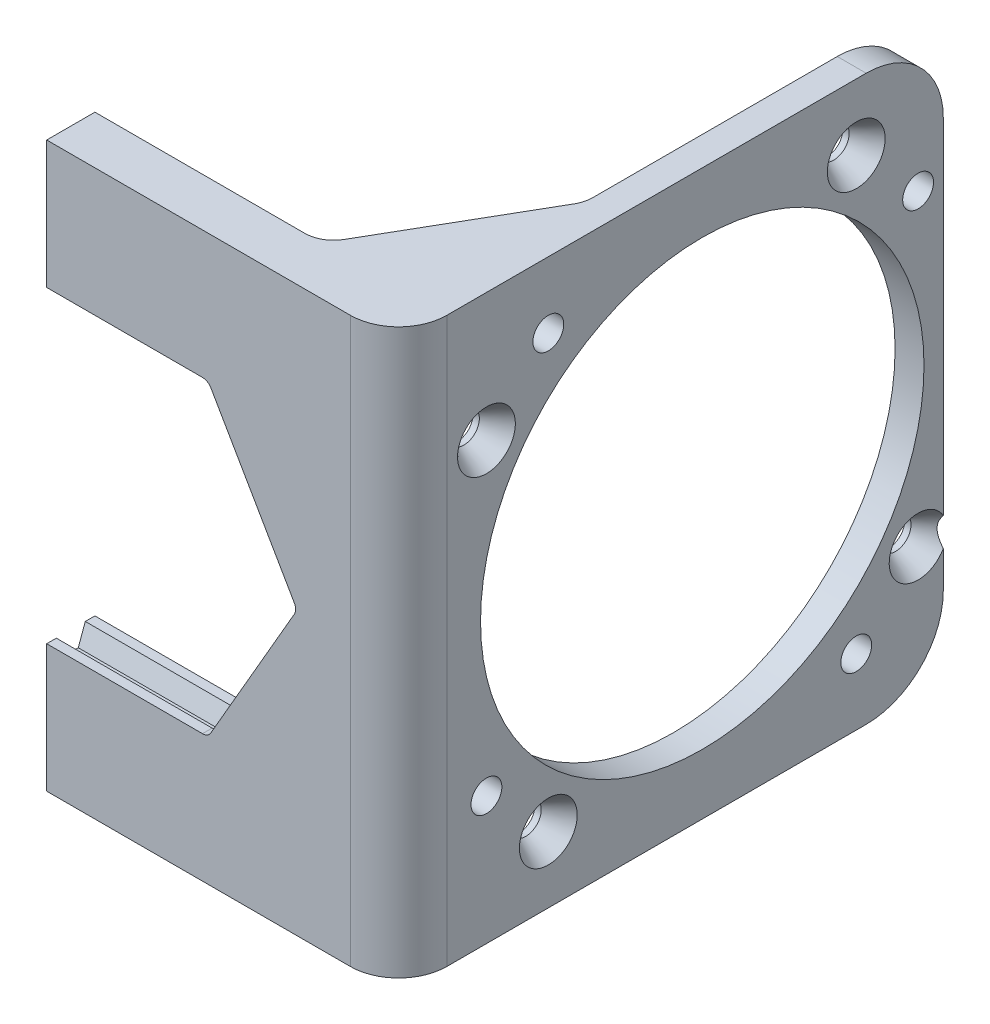
SolidWorks part; units mm, degrees
material "6061 合金"
ref_plane "前视基准面" through (0, 0, 0) normal (0, 0, 1) x (1, 0, 0)
ref_plane "上视基准面" through (0, 0, 0) normal (0, 1, 0) x (1, 0, 0)
ref_plane "右视基准面" through (0, 0, 0) normal (1, 0, 0) x (0, 0, -1)
other "Configuration Table"
sketch "草图1" plane through (0, 0, 0) normal (0, 0, 1) x (1, 0, 0)
  line L0 (-10.7623, 0) -> (8.7048, 0) construction
  line L1 (0, 6.2516) -> (0, -8.3883) construction
  circle A0 centre (0, 0) radius 18
  dimension "D1" = 36
extrude "凸台-拉伸1" add sketch "草图1" along normal blind 5
sketch "草图8" plane through (0, 0, 0) normal (0, 0, 1) x (1, 0, 0)
  line L0 (37.5243, 0) -> (-36.7763, 0) construction
  line L1 (0, 34.2207) -> (0, -32.974) construction
  line L2 (0, 26.25) -> (31, 26.25)
  line L3 (31, 26.25) -> (31, -26.25)
  line L4 (31, -26.25) -> (0, -26.25)
  line L5 (0, -26.25) -> (0, -18)
  line L6 (0, 26.25) -> (0, 18)
  circle A0 centre (0, 0) radius 18 construction
  arc A1 (0, -18) -> (0, 18) centre (0, 0) ccw
  dimension "D1" = 52.5
  dimension "D2" = 31
extrude "凸台-拉伸2" add sketch "草图8" along normal up to surface (5 mm away) up to face at (18, 0, 5)
sketch "草图9" plane through (0, 0, 0) normal (0, 0, -1) x (-1, 0, 0)
  line L0 (-31, 26.25) -> (0, 26.25) construction
  line L1 (-31, -26.25) -> (-26, -26.25)
  line L2 (-31, -26.25) -> (-31, 26.25)
  line L3 (-31, 26.25) -> (-26, 26.25)
  line L4 (-26, -26.25) -> (-26, 26.25)
  dimension "D1" = 5
extrude "凸台-拉伸3" add sketch "草图9" along normal blind 51.5
sketch "草图12" plane through (31, 0, 0) normal (1, 0, 0) x (0, 0, -1)
  line L1 (26.5, 0) -> (48.8882, 15.9693) construction
  line L2 (42.4693, 22.3882) -> (26.5, 0) construction
  line L3 (-6.3808, 0) -> (26.5, 0) construction
  line L4 (26.5, 0) -> (4.1118, 15.9693) construction
  line L5 (-5, -26.25) -> (-5, 26.25) construction
  circle A0 centre (26.5, 0) radius 27.5 construction
  circle A1 centre (4.1118, 15.9693) radius 1.6
  circle A2 centre (42.4693, 22.3882) radius 1.6
  circle A3 centre (48.8882, -15.9693) radius 1.6
  circle A4 centre (10.5307, -22.3882) radius 1.6
  circle A5 centre (48.8882, 15.9693) radius 1.6
  circle A6 centre (42.4693, -22.3882) radius 1.6
  circle A7 centre (4.1118, -15.9693) radius 1.6
  circle A8 centre (10.5307, 22.3882) radius 1.6
  point P22 (26.5, 0)
  point P27 (26.5, 0)
  dimension "D2" = 55
  dimension "D4" = 3.2
  dimension "D1" = 31.5
  dimension "D3" = 35.5
  dimension "D6" = 19
  dimension "D5" = 4
  dimension "D7" = 4
extrude "切除-拉伸1" cut sketch "草图12" against normal blind 45
sketch "草图25" plane through (0, 0, 0) normal (0, 0, -1) x (-1, 0, 0)
  line L0 (0, 16) -> (0, 26.25)
  line L1 (18.4752, 0) -> (9.2376, 16)
  line L2 (9.2376, 16) -> (-9.2376, 16)
  line L3 (-9.2376, 16) -> (-18.4752, 0)
  line L4 (-18.4752, 0) -> (-9.2376, -16)
  line L5 (-9.2376, -16) -> (9.2376, -16)
  line L6 (9.2376, -16) -> (18.4752, 0)
  line L7 (0, 26.25) -> (23.9717, 26.25)
  line L8 (23.9717, 26.25) -> (23.9717, -26.25)
  line L9 (23.9717, -26.25) -> (0, -26.25)
  line L10 (0, -26.25) -> (0, -16)
  circle A0 centre (0, 0) radius 16 construction
  line M6 (0, -26.25) -> (0, -18)
  arc M7 (0, -18) -> (0, 18) centre (0, 0) ccw
  line M8 (0, 18) -> (0, 26.25)
  dimension "D1" = 32
extrude "切除-拉伸7" cut sketch "草图25" against normal blind 10 contours L9 L8 L7 L2 L1 L6 L5 M8 M7 M6 | L1 M7 | L2 L0 M7 | L6 M7 | L10 L5 M7 region at (-3.1166, 16.8039, 0) region at (-0.5771, 22.125, 0) region at (-14.5526, 8.402, 0) region at (-3.1166, -16.8039, 0) region at (-14.5526, -8.402, 0)
extrude "切除-拉伸8" cut sketch "草图25<3>" against normal blind 10 contours L6 L1 L2 L3 L4 L5 M7 | L1 | L5 | L3 region at (0.0165, 0, 0) region at (-9.077, 15.7217, 0) region at (-9.077, -15.7217, 0)
sketch "草图25<3>" plane through (0, 0, 0) normal (0, 0, -1) x (-1, 0, 0) same geometry as "草图25"
sketch "草图26" plane through (0, 0, 0) normal (0, 0, -1) x (-1, 0, 0)
  line L0 (0, 26.25) -> (7.5, 26.25)
  line L1 (7.5, 26.25) -> (7.5, 16)
  line L2 (7.5, 16) -> (0, 16)
  line L3 (0, 16) -> (0, 26.25)
  line L4 (0, -16) -> (7.5, -16)
  line L5 (0, -16) -> (0, -26.25) construction
  line L6 (0, -16) -> (0, -26.25)
  line L7 (0, -26.25) -> (7.5, -26.25)
  line L8 (7.5, -26.25) -> (7.5, -16)
  dimension "D1" = 7.5
extrude "凸台-拉伸5" add sketch "草图26" against normal up to surface (5 mm away) up to face at (10.9945, 0, 5)
sketch "草图27" plane through (-7.5, 0, 0) normal (-1, 0, 0) x (0, 0, 1)
  line L0 (2.5, 16) -> (2.5, 50016) construction
  line L1 (5, 16) -> (0, 16) construction
  line L2 (1, 16) -> (1.7279, 18)
  line L3 (5, 16) -> (0, 16) construction
  line L4 (1.7279, 18) -> (2.5, 18)
  line L5 (3.2721, 18) -> (2.5, 18)
  line L6 (4, 16) -> (3.2721, 18)
  line L7 (1, 16) -> (4, 16)
  point P4 (2.5, 16)
  dimension "D1" = 3
  dimension "D2" = 40
  dimension "D3" = 2
ref_plane "基准面1" through (0, 0, 2.5) normal (0, 0, 1) x (1, 0, 0)
sketch "草图28" plane through (0, 0, 2.5) normal (0, 0, 1) x (1, 0, 0)
  line L0 (-7.5, -199984) -> (-7.5, 250016) construction
  line L1 (18.4752, 0) -> (9.2376, 16)
  line L2 (9.2376, 16) -> (-9.2376, 16)
  line L3 (-9.2376, 16) -> (-18.4752, 0)
  line L4 (-18.4752, 0) -> (-9.2376, -16)
  line L5 (-9.2376, -16) -> (9.2376, -16)
  line L6 (9.2376, -16) -> (18.4752, 0)
  circle A0 centre (0, 0) radius 16 construction
  dimension "D1" = 32
sweep "切除-扫描1" cut profiles "草图27" path "草图28"
fillet "圆角11" radius 1 12 edges at (10.3923, 18, 2.114) (10.3923, -18, 2.114) (20.7846, 0, 2.114) (9.2376, 16, 4.5) (10.3923, 18, 2.886) (9.2376, 16, 0.5) (9.2376, -16, 4.5) (10.3923, -18, 2.886) (9.2376, -16, 0.5) (18.4752, 0, 4.5) (20.7846, 0, 2.886) (18.4752, 0, 0.5)
sketch "草图14" plane through (31, 0, 0) normal (1, 0, 0) x (0, 0, -1)
  circle A0 centre (26.5, 0) radius 23
  dimension "D1" = 46
extrude "切除-拉伸2" cut sketch "草图14" against normal through all
sketch "草图21" plane through (0, 26.25, 0) normal (0, 1, 0) x (1, 0, 0)
  line L2 (26, 51.5) -> (26, 0) construction
  line L5 (-7.5, 0) -> (16, 0)
  line L6 (-7.5, -5) -> (31, -5)
  line L7 (31, -5) -> (31, 51.5)
  line L8 (31, 51.5) -> (26, 51.5)
  line L9 (26, 51.5) -> (26, 0)
  line L10 (26, 0) -> (-7.5, 0)
  line L12 (-7.5, -5) -> (31, -5)
  line L13 (31, -5) -> (31, 51.5)
  line L14 (31, 51.5) -> (26, 51.5)
  line L18 (26, 0) -> (-7.5, 0) construction
  line L19 (16, 0) -> (26, 17.3205)
  line L20 (26, 17.3205) -> (26, 51.5)
  line L29 (-7.5, 0) -> (-7.5, -5)
  line L30 (-7.5, 0) -> (-7.5, -5)
  dimension "D2" = 60
  dimension "D3" = 10
  dimension "D1" = 0
extrude "凸台-拉伸4" add sketch "草图21" along normal blind 3
mirror "镜向1" about plane through (0, 0, 0) normal (0, 1, 0) of "凸台-拉伸4"
sketch "草图36" plane through (31, 0, 0) normal (1, 0, 0) x (0, 0, -1)
  line L4 (-5, 29.25) -> (-5, -29.25)
  line L5 (-5, -29.25) -> (51.5, -29.25)
  line L6 (51.5, -29.25) -> (51.5, 29.25)
  line L7 (51.5, 29.25) -> (-5, 29.25)
  line L8 (-5, 29.25) -> (-5, -29.25)
  line L9 (-5, -29.25) -> (51.5, -29.25)
  line L10 (51.5, -29.25) -> (51.5, 29.25)
  line L11 (51.5, 29.25) -> (-5, 29.25)
  dimension "D1" = 0
extrude "切除-拉伸10" cut sketch "草图36" against normal blind 2
fillet "圆角4" radius 5 1 edges at (29, 0, 5)
fillet "圆角6" radius 8 2 edges at (27.5, -29.25, -51.5) (27.5, 29.25, -51.5)
fillet "圆角9" radius 3 4 edges at (16, 27.75, 0) (16, -27.75, 0) (26, -27.75, -17.3205) (26, 27.75, -17.3205)
fillet "圆角10" radius 2 5 edges at (20.134, -26.25, 0) (26, -26.25, -9.0622) (26, 0, 0) (26, 26.25, -9.0622) (20.134, 26.25, 0)
sketch "草图29" plane through (-7.5, 0, 0) normal (-1, 0, 0) x (0, 0, 1)
  line L0 (0, 0) -> (50000, 0) construction
  line L1 (2.5, 28.5) -> (2.5, -49971.5) construction
  circle A0 centre (2.5, 20.8) radius 1.5
  circle A1 centre (2.5, -20.8) radius 1.5
  point P8 (2.5, 20.8)
  point P10 (2.5, -20.8)
  dimension "D2" = 3
  dimension "D1" = 20.8
hole_wizard "M3 螺纹孔1" positions "草图29" profile "草图31" tap size "M3" standard "GB"
sketch "草图31" plane through (-7.5, -20.8, 2.5) normal (0, 1, 0) x (0, 0, 1)
  line L0 (0, 0) -> (0, 6.2511)
  line L1 (0, 6.2511) -> (1.25, 5.5)
  line L2 (1.25, 5.5) -> (1.25, 0)
  line L5 (1.25, 0) -> (0, 0)
  line L10 (0, 6.2511) -> (-1.25, 5.5) construction
  line L11 (0, -6.35) -> (0, 107.95) construction
  dimension "螺纹孔钻头直径" = 2.5
  dimension "螺纹孔钻头深度" = 5.5
  dimension "导头角度" = 118
cosmetic thread "孔螺蚊线1" parameters "D1"=4, "D2"=3
cosmetic thread "孔螺蚊线2" parameters "D1"=4, "D2"=3
ref_axis "基准轴2" through (26, -22.3882, -10.5307) along (1, 0, 0)
ref_plane "基准面3" through (0, -22.3882, 0) normal (0, 1, 0) x (1, 0, 0)
sketch "草图40" plane through (0, -22.3882, 0) normal (0, 1, 0) x (1, 0, 0)
  line L0 (29, 10.5307) -> (26.0943, 10.5307) construction
  line L1 (26, 10.5307) -> (29, 10.5307) construction
  line L2 (29, 43.5) -> (29, 0) construction
  line L3 (29, 10.5307) -> (29, 13.5307)
  line L4 (29, 13.5307) -> (26.5, 12.0307)
  line L5 (26.5, 12.0307) -> (26.5, 10.5307)
  line L6 (26.5, 10.5307) -> (29, 10.5307)
  dimension "D1" = 6
  dimension "D2" = 3
  dimension "D3" = 2.5
revolve "切除-旋转2" cut sketch "草图40" angle 360 about L0
pattern_circular "阵列(圆周)2" count 4 every 90 about axis through (-7.5, 0, -26.5) along (1, 0, 0) of "切除-旋转2"
